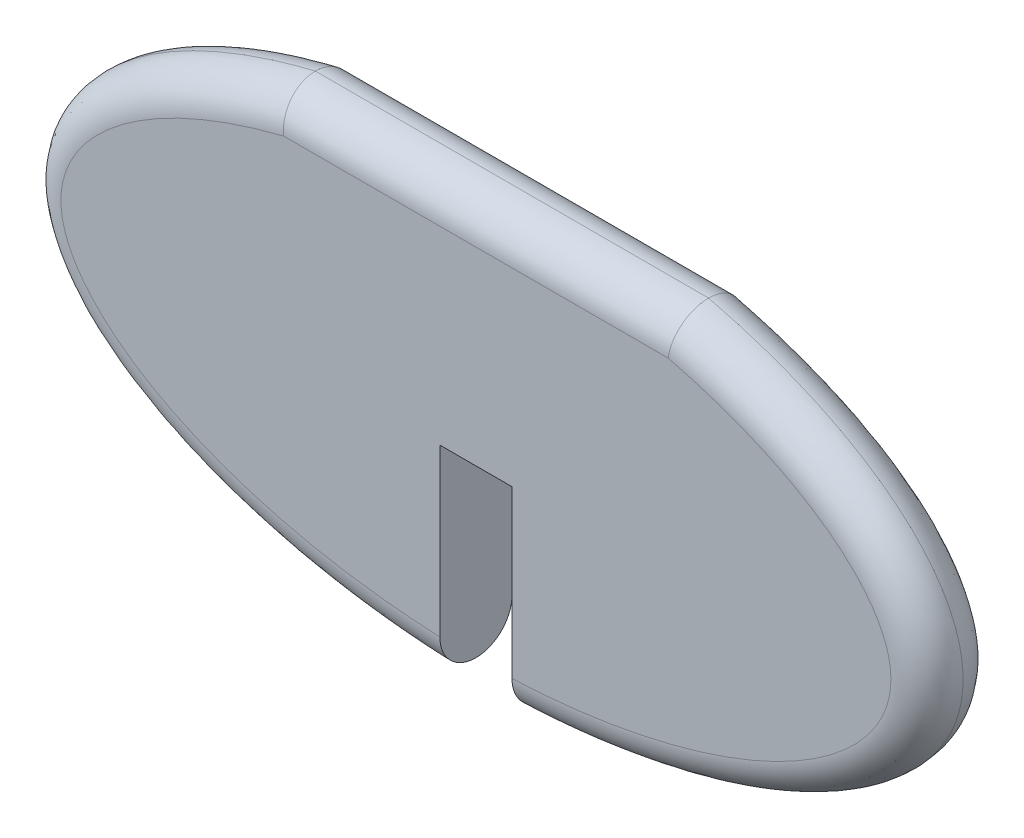
SolidWorks part; units mm, degrees
ref_plane "Front Plane" through (0, 0, 0) normal (0, 0, 1) x (1, 0, 0)
ref_plane "Top Plane" through (0, 0, 0) normal (0, 1, 0) x (1, 0, 0)
ref_plane "Right Plane" through (0, 0, 0) normal (1, 0, 0) x (0, 0, -1)
sketch "Sketch1" plane through (0, 0, 0) normal (0, 0, 1) x (1, 0, 0)
  line L0 (-21.7945, 22.5) -> (21.7945, 22.5)
  ellipse E0 centre (0, 0) end of major axis (50, 0) minor radius 25 (-21.7945, 22.5) -> (21.7945, 22.5) ccw
  dimension "D1" = 50
  dimension "D2" = 25
  dimension "D3" = 43.589
  dimension "D4" = 22.5
extrude "Boss-Extrude1" add sketch "Sketch1" along normal mid plane 8
sketch "Sketch2" plane through (0, 0, 4) normal (0, 0, 1) x (1, 0, 0)
  line L0 (21.7945, 22.5) -> (-21.7945, 22.5) construction
  line L1 (-4, -2.5) -> (4, -2.5)
  line L2 (-4, -2.5) -> (-4, -32.5)
  line L3 (-4, -32.5) -> (4, -32.5)
  line L4 (4, -2.5) -> (4, -32.5)
  point P6 (0, -2.5)
  dimension "D1" = 30
  dimension "D2" = 8
  dimension "D3" = 25
extrude "Cut-Extrude1" cut sketch "Sketch2" against normal through all
fillet "Fillet1" radius 4 6 edges at (-49.1425, -4.6102, -4) (-49.1425, -4.6102, 4) (49.1425, -4.6102, -4) (49.1425, -4.6102, 4) (0, 22.5, -4) (0, 22.5, 4)
